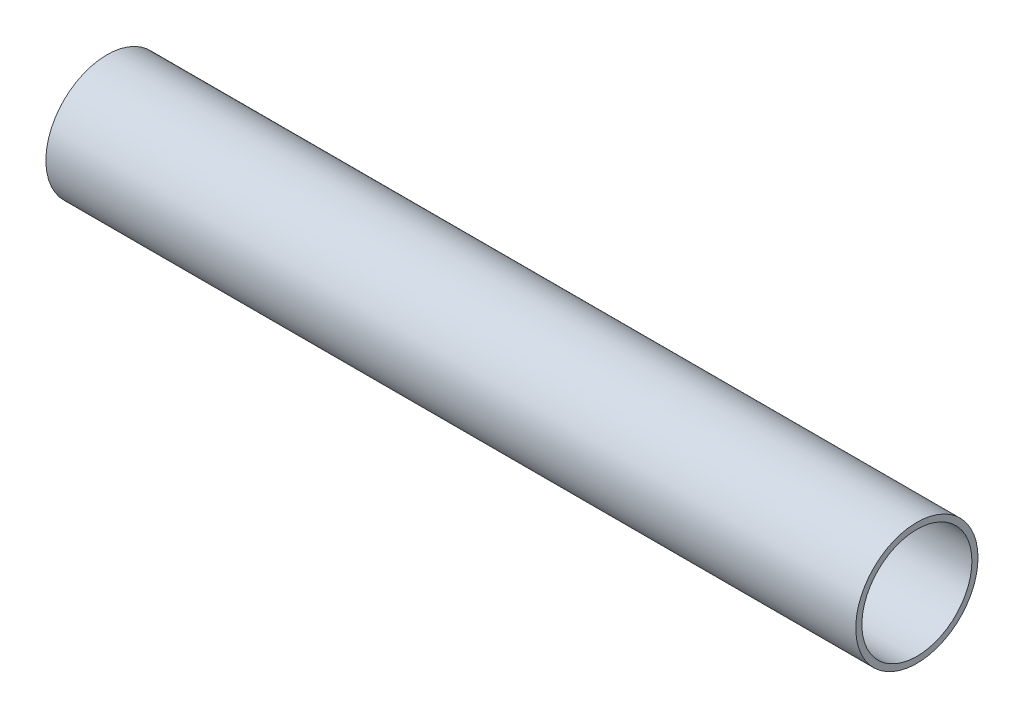
SolidWorks part; units mm, degrees
material "PC High Viscosity"
ref_plane "Front Plane" through (0, 0, 0) normal (0, 0, 1) x (1, 0, 0)
ref_plane "Top Plane" through (0, 0, 0) normal (0, 1, 0) x (1, 0, 0)
ref_plane "Right Plane" through (0, 0, 0) normal (1, 0, 0) x (0, 0, -1)
sketch "Sketch1" plane through (0, 0, 0) normal (1, 0, 0) x (0, 0, -1)
  circle A0 centre (0, 0) radius 15.875
  dimension "D1" = 31.75
extrude "Extrude-Thin1" add sketch "Sketch1" along normal mid plane 210.349 thin thin type one direction reverse wall 1.5875
